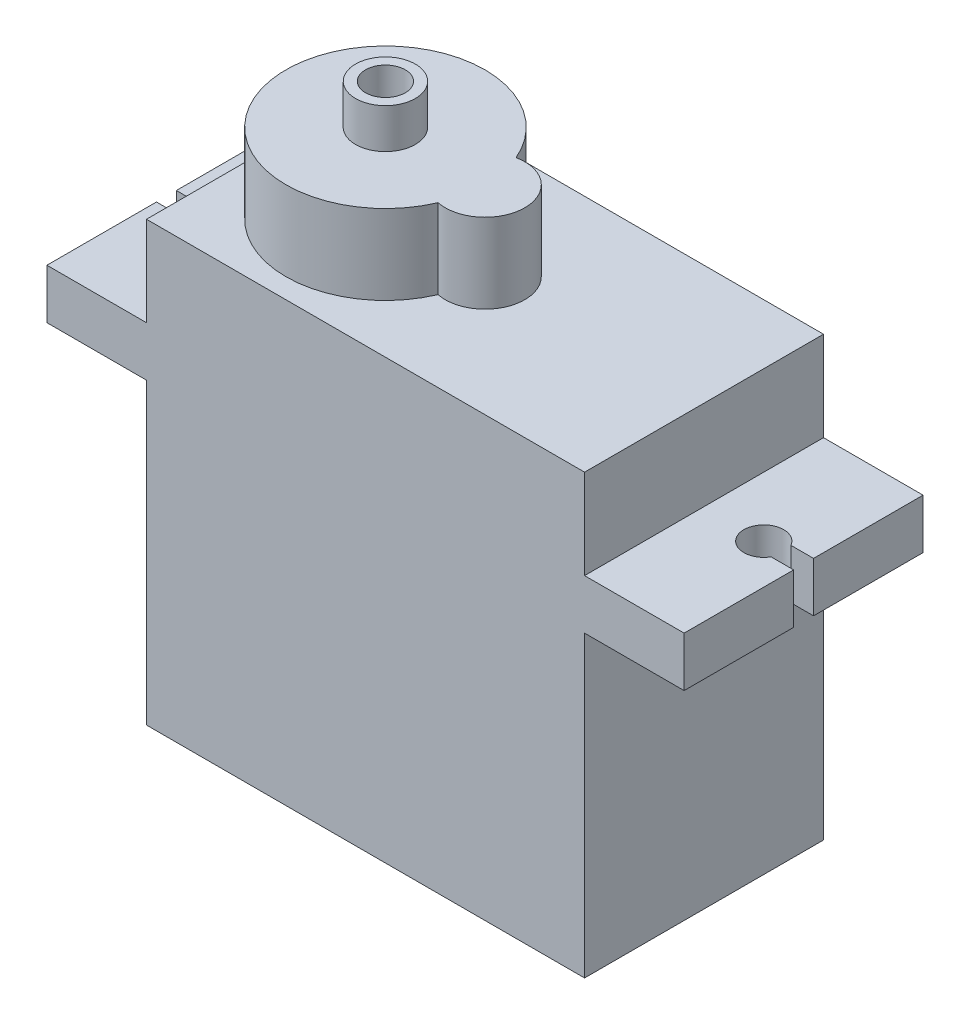
SolidWorks part; units mm, degrees
ref_plane "Front Plane" through (0, 0, 0) normal (0, 0, 1) x (1, 0, 0)
ref_plane "Top Plane" through (0, 0, 0) normal (0, 1, 0) x (1, 0, 0)
ref_plane "Right Plane" through (0, 0, 0) normal (1, 0, 0) x (0, 0, -1)
sketch "Sketch1" plane through (0, 0, 0) normal (0, 1, 0) x (1, 0, 0)
  line L1 (-11, 6) -> (11, 6)
  line L2 (-11, 6) -> (-11, -6)
  line L3 (-11, -6) -> (11, -6)
  line L4 (11, 6) -> (11, -6)
  line L5 (-11, 6) -> (11, -6) construction
  line L6 (-11, -6) -> (11, 6) construction
  point P0 (0, 0)
  dimension "D1" = 22
  dimension "D2" = 12
extrude "Body" add sketch "Sketch1" along normal blind 22 contours L2 L3 L4 L1
ref_plane "Plane1" through (0, 22, 0) normal (0, 1, 0) x (1, 0, 0)
sketch "Sketch2" plane through (0, 22, 0) normal (0, 1, 0) x (1, 0, 0)
  arc A0 (-0.4, 1.9596) -> (-0.4, -1.9596) centre (-5, 0) ccw
  arc A1 (-0.4, -1.9596) -> (-0.4, 1.9596) centre (0, 0) ccw
  dimension "D1" = 10
  dimension "D3" = 4
  dimension "D2" = 5
extrude "Hub" add sketch "Sketch2" along normal blind 4 contours A0 A1
ref_plane "Plane2" through (0, 26, 0) normal (0, 1, 0) x (1, 0, 0)
sketch "Sketch3" plane through (0, 26, 0) normal (0, 1, 0) x (1, 0, 0)
  circle A0 centre (-5, 0) radius 1.5
  dimension "D1" = 3
extrude "Axle" add sketch "Sketch3" along normal blind 2
ref_plane "Plane3" through (0, 15, 0) normal (0, 1, 0) x (1, 0, 0)
sketch "Sketch4" plane through (0, 15, 0) normal (0, 1, 0) x (1, 0, 0)
  line L1 (-16, 6) -> (16, 6)
  line L2 (-16, 6) -> (-16, -6)
  line L3 (-16, -6) -> (16, -6)
  line L4 (16, 6) -> (16, -6)
  line L5 (-16, 6) -> (16, -6) construction
  line L6 (-16, -6) -> (16, 6) construction
  point P0 (0, 0)
  dimension "D1" = 12
  dimension "D2" = 32
extrude "Fin" add sketch "Sketch4" along normal blind 2.5
ref_plane "Plane4" through (-11, 0, 0) normal (-1, 0, 0) x (0, 0, 1)
sketch "Sketch5" plane through (-11, 0, 0) normal (-1, 0, 0) x (0, 0, 1)
  line L1 (-2, 4.5) -> (2, 4.5)
  line L2 (-2, 4.5) -> (-2, 3.5)
  line L3 (-2, 3.5) -> (2, 3.5)
  line L4 (2, 4.5) -> (2, 3.5)
  line L5 (-2, 4.5) -> (2, 3.5) construction
  line L6 (-2, 3.5) -> (2, 4.5) construction
  point P0 (0, 4)
  dimension "D1" = 4
  dimension "D2" = 1
  dimension "D3" = 4
extrude "Wire out" add sketch "Sketch5" along normal blind 0.5
sketch "Sketch6" plane through (0, 15, 0) normal (0, 1, 0) x (1, 0, 0)
  line L0 (-16, 6) -> (-16, -6) construction
  line L1 (0, -6.6) -> (0, 6.6) construction
  circle A0 centre (-14, 0) radius 1
  circle A1 centre (14, 0) radius 1
  point P4 (-16, 0)
  dimension "D1" = 2
  dimension "D2" = 2
extrude "Hole for screws" cut sketch "Sketch6" along normal up to next
ref_plane "Plane5" through (0, 28, 0) normal (0, 1, 0) x (1, 0, 0)
sketch "Sketch7" plane through (0, 28, 0) normal (0, 1, 0) x (1, 0, 0)
  circle A0 centre (-5, 0) radius 1
  dimension "D1" = 2
extrude "Cut-Extrude1" cut sketch "Sketch7" against normal blind 6 contours A0
sketch "Sketch8" plane through (0, 15, 0) normal (0, 1, 0) x (1, 0, 0)
  line L0 (-16.5, 0.5) -> (-14.5, 0.5)
  line L1 (-14.5, 0.5) -> (-14.5, -0.5)
  line L2 (-14.5, -0.5) -> (-16.5, -0.5)
  line L3 (-16.5, -0.5) -> (-16.5, 0.5)
  line L4 (-11, 6) -> (-16, 6) construction
  line L5 (-11, 6) -> (-11, -6) construction
  line L6 (0, -6.6) -> (0, 6.6) construction
  line L7 (14.5, 0.5) -> (14.5, -0.5)
  line L8 (16.5, 0.5) -> (14.5, 0.5)
  line L9 (16.5, -0.5) -> (16.5, 0.5)
  line L10 (14.5, -0.5) -> (16.5, -0.5)
  dimension "D1" = 1
  dimension "D2" = 2
  dimension "D3" = 5.5
  dimension "D4" = 3.5
extrude "Cut-Extrude2" cut sketch "Sketch8" along normal up to next
